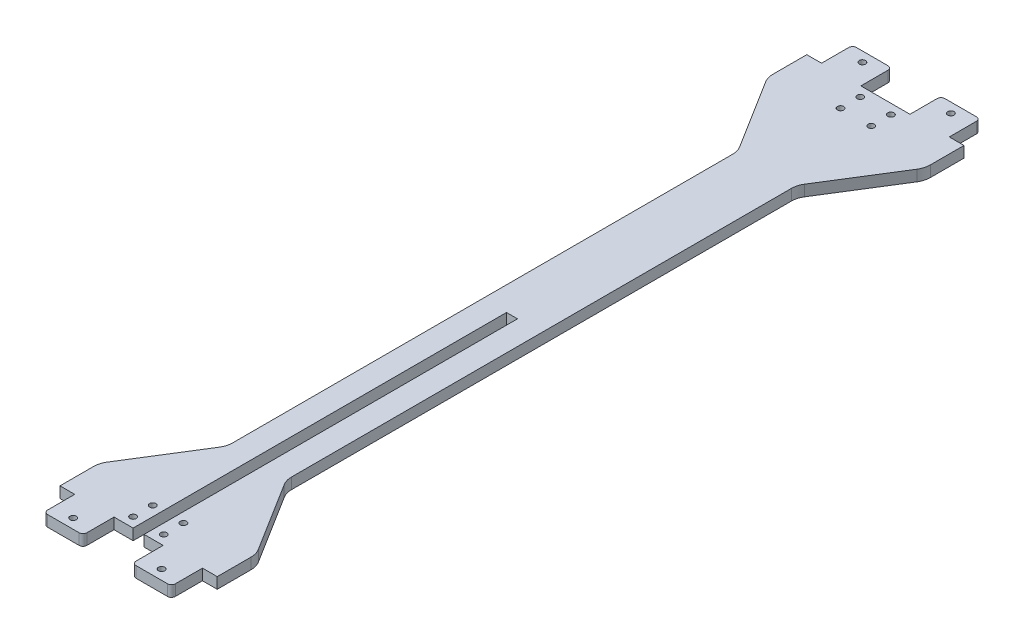
SolidWorks part; units mm, degrees
material "t5ハニカムプラダン"
ref_plane "正面" through (0, 0, 0) normal (0, 0, 1) x (1, 0, 0)
ref_plane "平面" through (0, 0, 0) normal (0, 1, 0) x (1, 0, 0)
ref_plane "右側面" through (0, 0, 0) normal (1, 0, 0) x (0, 0, -1)
sketch "ｽｹｯﾁ1" plane through (0, 0, 0) normal (0, 1, 0) x (1, 0, 0)
  line L0 (40, 380) -> (40, 0) construction
  line L1 (0, 0) -> (7.5, 0)
  line L2 (0, 0) -> (0, 380)
  line L3 (0, 380) -> (7.5, 380)
  line L4 (80, 0) -> (80, 380)
  line L5 (40, 190) -> (80, 190) construction
  line L6 (62.5, -15.8) -> (62.5, -10.8) construction
  line L7 (52.5, 0) -> (72.5, 0) construction
  line L8 (52.5, 0) -> (52.5, -13.8)
  line L9 (54.5, -15.8) -> (70.5, -15.8)
  line L10 (72.5, 0) -> (72.5, -13.8)
  line L11 (17.5, -15.8) -> (17.5, -10.8) construction
  line L12 (7.5, 0) -> (7.5, -13.8)
  line L13 (25.5, -15.8) -> (9.5, -15.8)
  line L14 (27.5, 0) -> (27.5, -13.8)
  line L15 (27.5, 0) -> (7.5, 0) construction
  line L16 (17.5, 395.8) -> (17.5, 390.8) construction
  line L17 (62.5, 395.8) -> (62.5, 390.8) construction
  line L18 (27.5, 380) -> (7.5, 380) construction
  line L19 (27.5, 380) -> (27.5, 393.8)
  line L20 (25.5, 395.8) -> (9.5, 395.8)
  line L21 (7.5, 380) -> (7.5, 393.8)
  line L22 (72.5, 380) -> (72.5, 393.8)
  line L23 (54.5, 395.8) -> (70.5, 395.8)
  line L24 (52.5, 380) -> (52.5, 393.8)
  line L25 (52.5, 380) -> (72.5, 380) construction
  line L26 (7.5, 380) -> (27.5, 380) construction
  line L27 (27.5, 380) -> (52.5, 380)
  line L28 (52.5, 380) -> (72.5, 380) construction
  line L29 (72.5, 380) -> (80, 380)
  line L30 (7.5, 0) -> (27.5, 0) construction
  line L31 (27.5, 0) -> (37.2, 0)
  line L32 (52.5, 0) -> (72.5, 0) construction
  line L33 (72.5, 0) -> (80, 0)
  line L34 (40, 0) -> (42.8, 0) construction
  line L35 (37.2, 0) -> (40, 0) construction
  line L36 (37.2, 0) -> (37.2, 190)
  line L37 (37.2, 190) -> (42.8, 190)
  line L38 (42.8, 0) -> (42.8, 190)
  line L39 (40, 0) -> (42.8, 0) construction
  line L40 (42.8, 0) -> (52.5, 0)
  line L41 (37.2, 0) -> (40, 0) construction
  line L42 (47.8, 375) -> (47.8, 365) construction
  circle A0 centre (62.5, -10.8) radius 1.6
  arc A1 (70.5, -15.8) -> (72.5, -13.8) centre (70.5, -13.8) ccw
  arc A2 (52.5, -13.8) -> (54.5, -15.8) centre (54.5, -13.8) ccw
  arc A3 (27.5, -13.8) -> (25.5, -15.8) centre (25.5, -13.8) cw
  arc A4 (9.5, -15.8) -> (7.5, -13.8) centre (9.5, -13.8) cw
  circle A5 centre (17.5, -10.8) radius 1.6
  circle A6 centre (17.5, 390.8) radius 1.6
  arc A7 (9.5, 395.8) -> (7.5, 393.8) centre (9.5, 393.8) ccw
  arc A8 (27.5, 393.8) -> (25.5, 395.8) centre (25.5, 393.8) ccw
  arc A9 (52.5, 393.8) -> (54.5, 395.8) centre (54.5, 393.8) cw
  arc A10 (70.5, 395.8) -> (72.5, 393.8) centre (70.5, 393.8) cw
  circle A11 centre (62.5, 390.8) radius 1.6
  circle A12 centre (47.8, 375) radius 1.6
  circle A13 centre (32.2, 375) radius 1.6
  circle A14 centre (47.8, 5) radius 1.6
  circle A15 centre (32.2, 5) radius 1.6
  circle A16 centre (47.8, 365) radius 1.6
  circle A17 centre (32.2, 365) radius 1.6
  circle A18 centre (47.8, 15) radius 1.6
  circle A19 centre (32.2, 15) radius 1.6
  point P18 (72.5, -15.8)
  point P21 (52.5, -15.8)
  point P33 (27.5, -15.8)
  point P34 (7.5, -15.8)
  point P57 (7.5, 395.8)
  point P58 (27.5, 395.8)
  point P59 (52.5, 395.8)
  point P60 (72.5, 395.8)
  dimension "D5" = 3.2
  dimension "D7" = 2
  dimension "D10" = 3.2
  dimension "D1" = 80
  dimension "D2" = 380
  dimension "D3" = 20
  dimension "D4" = 15.8
  dimension "D6" = 5
  dimension "D8" = 25
  dimension "D9" = 5.6
  dimension "D11" = 5
  dimension "D12" = 5
  dimension "D13" = 10
extrude "ﾎﾞｽ - 押し出し1" add sketch "ｽｹｯﾁ1" along normal blind 5.6
sketch "ｽｹｯﾁ2" plane through (0, 5.6, 0) normal (0, 1, 0) x (1, 0, 0)
  line L0 (40, 380) -> (40, 190) construction
  line L1 (52.5, 380) -> (27.5, 380) construction
  line L2 (37.2, 190) -> (42.8, 190) construction
  line L3 (40, 190) -> (80, 190) construction
  line L4 (80, 0) -> (80, 380) construction
  line L5 (72.5, 0) -> (80, 0) construction
  line L6 (80, 60) -> (55, 60) construction
  line L7 (80, 60) -> (80, 320)
  line L8 (80, 320) -> (55, 320) construction
  line L9 (55, 60) -> (55, 320)
  line L10 (25, 60) -> (25, 320)
  line L11 (0, 320) -> (25, 320) construction
  line L12 (0, 60) -> (0, 320)
  line L13 (0, 60) -> (25, 60) construction
  line L14 (55, 60) -> (80, 20)
  line L15 (80, 20) -> (80, 60)
  line L16 (0, 20) -> (0, 60)
  line L17 (25, 60) -> (0, 20)
  line L18 (80, 360) -> (80, 320)
  line L19 (55, 320) -> (80, 360)
  line L20 (0, 360) -> (0, 320)
  line L21 (25, 320) -> (0, 360)
  dimension "D1" = 60
  dimension "D2" = 30
  dimension "D3" = 20
extrude "ｶｯﾄ - 押し出し1" cut sketch "ｽｹｯﾁ2" against normal through all
fillet "ﾌｨﾚｯﾄ1" radius 10 8 edges at (80, 2.8, -360) (55, 2.8, -320) (0, 2.8, -360) (25, 2.8, -320) (25, 2.8, -60) (0, 2.8, -20) (80, 2.8, -20) (55, 2.8, -60)
